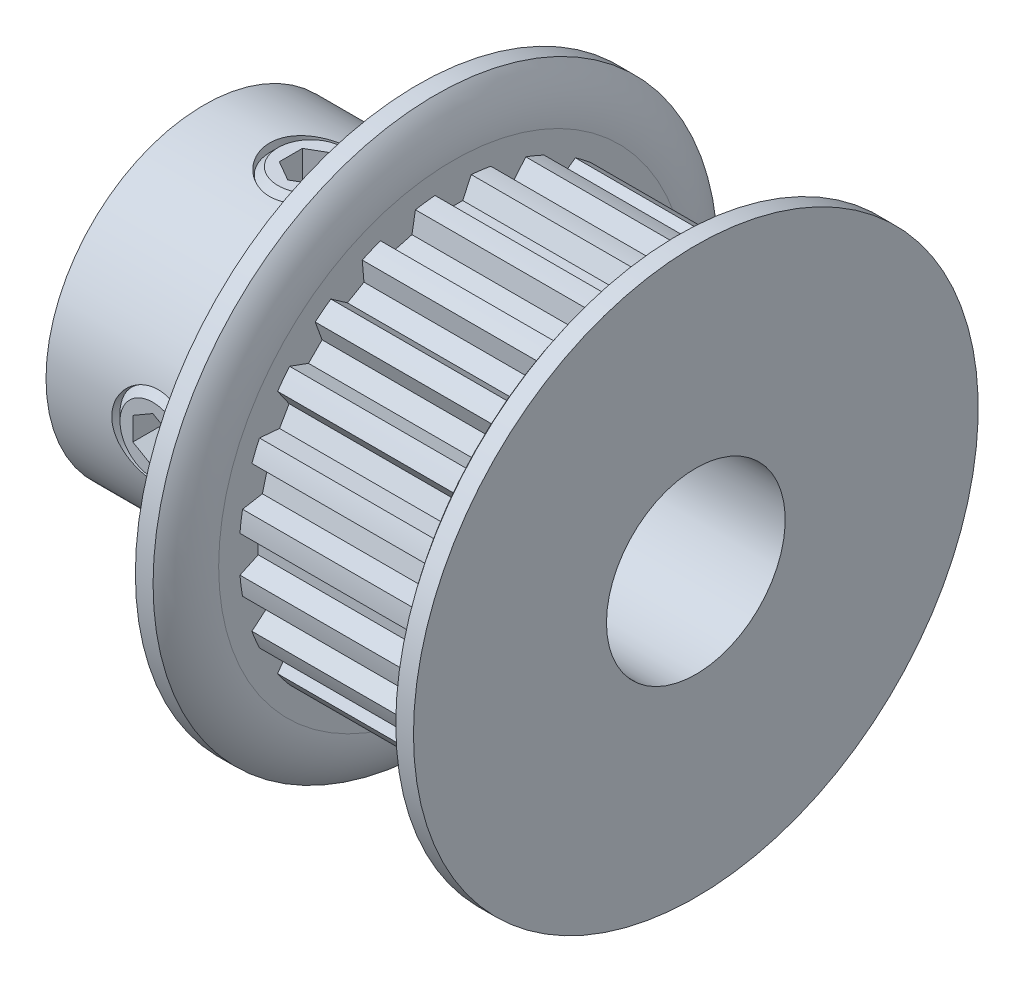
SolidWorks part; units mm, degrees
ref_plane "Front Plane" through (0, 0, 0) normal (0, 0, 1) x (1, 0, 0)
ref_plane "Top Plane" through (0, 0, 0) normal (0, 1, 0) x (1, 0, 0)
ref_plane "Right Plane" through (0, 0, 0) normal (1, 0, 0) x (0, 0, -1)
sketch "Sketch2" plane through (0, 0, 0) normal (1, 0, 0) x (0, 0, -1)
  line L3 (0, 0) -> (0, 6.9342) construction
  line L6 (0, -7.4422) -> (0, -7.7597) construction
  line L7 (-0.5715, 7.4202) -> (-0.341, 6.9258)
  line L8 (0.5715, 7.4202) -> (0.341, 6.9258)
  line L9 (-0.5715, 7.4202) -> (-0.6431, 7.5737)
  line L10 (0.5715, 7.4202) -> (0.6431, 7.5737)
  line L12 (-0.341, 6.9258) -> (0.341, 6.9258)
  line L14 (0, 7.4422) -> (0, 7.7597) construction
  line L15 (0, 0) -> (0, -1.143) construction
  circle A0 centre (0, 0) radius 7.7597 construction
  circle A1 centre (0, 0) radius 6.9342 construction
  circle A2 centre (0, 0) radius 7.4422 construction
  arc A7 (0.6431, 7.5737) -> (-0.6431, 7.5737) centre (0, 0) ccw
  point P5 (0, 7.6009)
  dimension "D3" = 0.3175
  dimension "D1" = 50
sketch "Sketch1" plane through (0, 0, 0) normal (0, 0, 1) x (1, 0, 0)
  line L0 (-8.7376, 0) -> (8.7376, 0) construction
  line L1 (-8.7376, 3.175) -> (8.7376, 3.175)
  line L2 (-8.7376, 3.175) -> (-8.7376, 5.6134)
  line L3 (-1.143, 10.033) -> (-0.5144, 10.033)
  line L4 (0.1143, 7.7597) -> (0.1143, 8.3312)
  line L5 (0.1143, 8.9027) -> (0.1143, 7.7597) construction
  line L6 (0.1143, 7.7597) -> (7.4803, 7.7597)
  line L7 (7.4803, 7.7597) -> (7.4803, 8.3312)
  line L8 (7.4803, 7.7597) -> (8.7376, 7.7597) construction
  line L9 (8.1089, 10.033) -> (8.7376, 10.033)
  line L10 (8.7376, 10.033) -> (8.7376, 3.175)
  line L11 (8.1089, 7.7597) -> (8.1089, 10.033) construction
  line L12 (-4.9403, 5.6134) -> (-4.9403, 3.175) construction
  line L13 (-1.143, 10.033) -> (-1.143, 5.6134)
  line L14 (-1.143, 5.6134) -> (-8.7376, 5.6134)
  arc A0 (7.4803, 8.3312) -> (8.1089, 10.033) centre (10.0981, 8.3312) cw
  arc A1 (0.1143, 8.3312) -> (-0.5144, 10.033) centre (-2.5035, 8.3312) ccw
  dimension "Bore Size" = 6.35
  dimension "Overall Width" = 17.4752
  dimension "Inside Width" = 7.366
  dimension "OD" = 20.066
  dimension "D2" = 15.5194
  dimension "D3" = 1.143
  dimension "D4" = 0.5715
  dimension "Outside Width" = 9.8806
revolve "Revolve1" add sketch "Sketch1" angle 360 mid plane about L0
sketch "Sketch4" plane through (0.1143, 0, 0) normal (1, 0, 0) x (0, 0, -1)
  circle A0 centre (0, 0) radius 7.601
  circle A2 centre (0, 0) radius 7.7597
  circle A3 centre (0, 0) radius 7.7597 construction
extrude "Cut-Extrude2" cut sketch "Sketch4" along normal up to surface (7.366 mm away) up to face at (7.4803, 0, 7.7597)
sketch "Sketch3" plane through (0.1143, 0, 0) normal (1, 0, 0) x (0, 0, -1)
  line L2 (-0.5715, 7.4202) -> (-0.341, 6.9258) construction
  line L3 (-0.341, 6.9258) -> (0.341, 6.9258) construction
  line L4 (0.5715, 7.4202) -> (0.341, 6.9258) construction
  line L5 (-0.6431, 7.5737) -> (-0.341, 6.9258)
  line L6 (-0.341, 6.9258) -> (0.341, 6.9258)
  line L7 (0.6431, 7.5737) -> (0.341, 6.9258)
  arc A1 (0.6431, 7.5737) -> (-0.6431, 7.5737) centre (0, 0) ccw construction
  arc A2 (0.6431, 7.5737) -> (-0.6431, 7.5737) centre (0, 0) ccw
extrude "Cut-Extrude1" cut sketch "Sketch3" along normal up to surface (7.366 mm away) up to face at (7.4803, 0, 8.3312)
pattern_circular "CirPattern1" count 24 over 360 of "Cut-Extrude1"
sketch "Sketch5" plane through (0, 0, 0) normal (0, 0, 1) x (1, 0, 0)
  line L1 (7.4803, 8.3312) -> (7.4803, -8.3312) construction
  point P0 (7.4803, 0)
sketch "Sketch6" plane through (0, 0, 0) normal (0, 1, 0) x (1, 0, 0)
  line L0 (-8.7376, 0) -> (-6.4008, 0) construction
  line L1 (-8.7376, 10.033) -> (-8.7376, -10.033) construction
  line L2 (-1.143, 0) -> (-3.4798, 0) construction
  line L4 (-1.143, 10.033) -> (-1.143, -10.033) construction
  circle A0 centre (-4.9403, 0) radius 1.4605
  dimension "D1" = 2.921
extrude "Cut-Extrude3" cut sketch "Sketch6" along normal through all
sketch "Sketch7" plane through (0, 0, 0) normal (0, 0, 1) x (1, 0, 0)
  line L0 (-6.1087, 5.6134) -> (-4.9403, 5.6134)
  line L1 (-6.3627, 5.3594) -> (-6.3627, 3.81)
  line L2 (-6.3627, 3.81) -> (-6.1087, 3.556)
  line L3 (-6.1087, 3.556) -> (-4.9403, 3.556)
  line L4 (-4.9403, 3.556) -> (-4.9403, 5.6134) construction
  line L5 (-1.143, 5.6134) -> (-8.7376, 5.6134) construction
  line L6 (-6.3627, 5.3594) -> (-6.1087, 5.6134)
  line L8 (-4.9403, 5.6134) -> (-4.9403, 3.556)
  point P0 (-6.3627, 5.6134)
  point P4 (-6.3627, 3.556)
  dimension "D1" = 2.8448
  dimension "D2" = 0.381
revolve "Revolve2" add sketch "Sketch7" angle 360 mid plane about L4
sketch "Sketch8" plane through (0, 5.6134, 0) normal (0, 1, 0) x (1, 0, 0)
  line L1 (-4.9403, 0.8212) -> (-5.6515, 0.4106)
  line L2 (-5.6515, 0.4106) -> (-5.6515, -0.4106)
  line L3 (-5.6515, -0.4106) -> (-4.9403, -0.8212)
  line L4 (-4.9403, -0.8212) -> (-4.2291, -0.4106)
  line L5 (-4.2291, -0.4106) -> (-4.2291, 0.4106)
  line L6 (-4.2291, 0.4106) -> (-4.9403, 0.8212)
  circle A0 centre (-4.9403, 0) radius 0.7112 construction
  dimension "D1" = 1.4224
extrude "Cut-Extrude4" cut sketch "Sketch8" against normal blind 1.016
pattern_circular "CirPattern2" count 2 over 90 about axis through (-8.7376, 0, 0) along (-1, 0, 0) of "Cut-Extrude3" reverse direction yes
pattern_circular "CirPattern3" count 2 over 90 reverse direction yes of bodies 107
equation "\"D3@Sketch2\" = (\"hs@Sketch2\"-\"ht@Sketch2\")/2"
equation "\"D2@Sketch1\" = \"PD@Sketch2\""
equation "\"D3@Sketch1\" = \"hs@Sketch2\""
equation "\"D4@Sketch1\" = \"D3@Sketch1\"/2"
